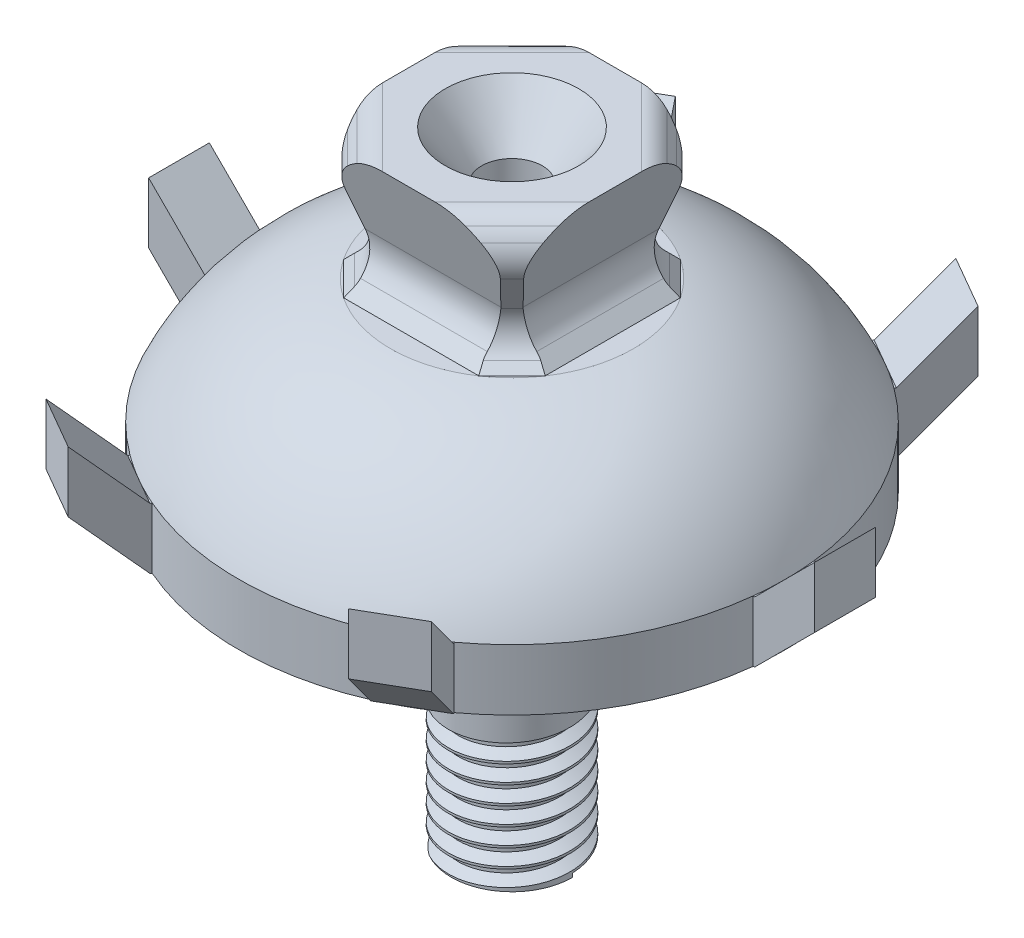
SolidWorks part; units mm, degrees
material "Commercially Pure CP-Ti UNS R50400 (SS)"
ref_plane "Front Plane" through (0, 0, 0) normal (0, 0, 1) x (1, 0, 0)
ref_plane "Top Plane" through (0, 0, 0) normal (0, 1, 0) x (1, 0, 0)
ref_plane "Right Plane" through (0, 0, 0) normal (1, 0, 0) x (0, 0, -1)
sketch "Sketch4" plane through (0, 0, 0) normal (0, 0, 1) x (1, 0, 0)
  line L1 (-8.5, -5.5) -> (8.5, -5.5)
  line L2 (-8.5, -5.5) -> (-8.5, 5.5)
  line L3 (-8.5, 5.5) -> (8.5, 5.5)
  line L4 (8.5, -5.5) -> (8.5, 5.5)
  line L5 (-8.5, -5.5) -> (8.5, 5.5) construction
  line L6 (-8.5, 5.5) -> (8.5, -5.5) construction
  point P0 (0, 0)
  dimension "D1" = 11
  dimension "D2" = 17
extrude "Boss-Extrude2" add sketch "Sketch4" along normal mid plane 17
sketch "Sketch5" plane through (0, 0, 0) normal (1, 0, 0) x (0, 0, -1)
  line L0 (0, -10) -> (0, 10) construction
  line L1 (8.5, 5.5) -> (6.5025, -1.2915)
  line L2 (8.5, -5.5) -> (7.2593, -4.2593)
  line L3 (-8.5, -5.5) -> (-7.2593, -4.2593)
  line L4 (-8.5, 5.5) -> (-6.5025, -1.2915)
  line L5 (-8.5, 5.5) -> (-8.5, -5.5)
  line L6 (8.5, -5.5) -> (8.5, 5.5)
  arc A0 (7.2593, -4.2593) -> (6.5025, -1.2915) centre (9.3806, -2.138) cw
  arc A1 (-7.2593, -4.2593) -> (-6.5025, -1.2915) centre (-9.3806, -2.138) ccw
  point P12 (6, -3)
  point P16 (-6, -3)
  dimension "D5" = 3
  dimension "D1" = 10
  dimension "D2" = 20
  dimension "D3" = 6
  dimension "D4" = 45
extrude "Cut-Extrude1" cut sketch "Sketch5" against normal mid plane 27
sketch "Sketch7" plane through (0, 0, 0) normal (0, 0, 1) x (1, 0, 0)
  line L0 (0, -10) -> (0, 10) construction
  line L1 (8.5, 5.5) -> (6.5025, -1.2915)
  line L2 (8.5, -5.5) -> (7.2593, -4.2593)
  line L3 (-8.5, -5.5) -> (-7.2593, -4.2593)
  line L4 (-8.5, 5.5) -> (-6.5025, -1.2915)
  line L5 (-8.5, 5.5) -> (-8.5, -5.5)
  line L6 (8.5, -5.5) -> (8.5, 5.5)
  line L7 (8.5, -4.2593) -> (8.5, -5.5) construction
  arc A0 (7.2593, -4.2593) -> (6.5025, -1.2915) centre (9.3806, -2.138) cw
  arc A1 (-7.2593, -4.2593) -> (-6.5025, -1.2915) centre (-9.3806, -2.138) ccw
  point P12 (-6, -3)
  dimension "D3" = 3
  dimension "D1" = 20
  dimension "D2" = 45
  dimension "D4" = 16.389
extrude "Cut-Extrude2" cut sketch "Sketch7" against normal mid plane 27
sketch "Sketch8" plane through (0, 5.5, 0) normal (0, 1, 0) x (1, 0, 0)
  line L0 (3.5355, 3.5355) -> (-3.5355, -3.5355) construction
  line L1 (-5, 0) -> (5, 0) construction
  line L2 (-3.5355, 3.5355) -> (3.5355, -3.5355) construction
  line L3 (0, 5) -> (0, -5) construction
  dimension "D1" = 10
  dimension "D2" = 10
  dimension "D3" = 10
  dimension "D4" = 45
  dimension "D5" = 45
  dimension "D6" = 10
sketch "Sketch9" plane through (0, 0, 0) normal (0, 1, 0) x (1, 0, 0)
  line L0 (3.5355, 3.5355) -> (-3.5355, -3.5355) construction
  line L1 (-5, 0) -> (5, 0) construction
  line L2 (-3.5355, 3.5355) -> (3.5355, -3.5355) construction
  line L3 (0, 5) -> (0, -5) construction
  point P8 (0, 0)
  point P10 (0, 0)
  point P11 (0, 0)
  dimension "D1" = 10
  dimension "D2" = 10
  dimension "D3" = 10
  dimension "D4" = 45
  dimension "D5" = 45
  dimension "D6" = 10
ref_plane "Plane1" through (0, 0, 0) normal (0.7071, 0, 0.7071) x (0.7071, 0, -0.7071)
ref_plane "Plane2" through (0, 0, 0) normal (0.7071, 0, -0.7071) x (-0.7071, 0, -0.7071)
sketch "Sketch11" plane through (0, 0, 0) normal (0.7071, 0, 0.7071) x (0.7071, 0, -0.7071)
  line L0 (-10, 5.5) -> (10, 5.5) construction
  line L1 (0, -5.5) -> (0, 5.5) construction
  line L2 (10, 5.5) -> (10, -5.5) construction
  line L3 (0, -5.5) -> (12.0208, -5.5) construction
  line L4 (10, -5.5) -> (0, -5.5) construction
  line L5 (10, -5.5) -> (9.1595, -4.6595)
  line L6 (10, 5.5) -> (10, 2.3) construction
  line L7 (0, 5.5) -> (8.25, 5.5) construction
  line L8 (9.6935, 1.5413) -> (8.4993, -1.4144)
  line L10 (10, -5.5) -> (14, -5.5)
  line L11 (14, -5.5) -> (14, 5.5)
  line L12 (14, 5.5) -> (8.25, 5.5)
  line L13 (-14, 5.5) -> (-8.25, 5.5)
  line L14 (-9.6935, 1.5413) -> (-8.4993, -1.4144)
  line L15 (-10, -5.5) -> (-9.1595, -4.6595)
  line L16 (-10, -5.5) -> (-14, -5.5)
  line L17 (-14, -5.5) -> (-14, 5.5)
  arc A0 (9.5819, 4.0331) -> (8.25, 5.5) centre (6.1993, 2.3) ccw
  arc A1 (9.5819, 4.0331) -> (9.6935, 1.5413) centre (6.9119, 2.6651) cw
  arc A2 (9.1595, -4.6595) -> (8.4993, -1.4144) centre (11.2808, -2.5382) cw
  arc A3 (-9.5819, 4.0331) -> (-9.6935, 1.5413) centre (-6.9119, 2.6651) ccw
  arc A4 (-9.5819, 4.0331) -> (-8.25, 5.5) centre (-6.1993, 2.3) cw
  arc A5 (-9.1595, -4.6595) -> (-8.4993, -1.4144) centre (-11.2808, -2.5382) ccw
  dimension "D7" = 3
  dimension "D8" = 3
  dimension "D1" = 20
  dimension "D2" = 11
  dimension "D3" = 45
  dimension "D4" = 8.25
  dimension "D5" = 3.2
  dimension "D6" = 22
  dimension "D9" = 4
extrude "Cut-Extrude3" cut sketch "Sketch11" against normal mid plane 27
sketch "Sketch12" plane through (0, 0, 0) normal (0.7071, 0, -0.7071) x (-0.7071, 0, -0.7071)
  line L0 (-10, 5.5) -> (10, 5.5) construction
  line L1 (0, -5.5) -> (0, 5.5) construction
  line L2 (10, 5.5) -> (10, -5.5) construction
  line L3 (10, -5.5) -> (0, -5.5) construction
  line L4 (10, -5.5) -> (9.1595, -4.6595)
  line L5 (10, 5.5) -> (10, 2.3) construction
  line L6 (0, 5.5) -> (8.25, 5.5) construction
  line L7 (9.6935, 1.5413) -> (8.4993, -1.4144)
  line L8 (10, -5.5) -> (14, -5.5)
  line L9 (14, -5.5) -> (14, 5.5)
  line L10 (14, 5.5) -> (8.25, 5.5)
  line L11 (-14, 5.5) -> (-8.25, 5.5)
  line L12 (-9.6935, 1.5413) -> (-8.4993, -1.4144)
  line L13 (-10, -5.5) -> (-9.1595, -4.6595)
  line L14 (-10, -5.5) -> (-14, -5.5)
  line L15 (-14, -5.5) -> (-14, 5.5)
  arc A0 (9.5819, 4.0331) -> (8.25, 5.5) centre (6.1993, 2.3) ccw
  arc A1 (9.5819, 4.0331) -> (9.6935, 1.5413) centre (6.9119, 2.6651) cw
  arc A2 (9.1595, -4.6595) -> (8.4993, -1.4144) centre (11.2808, -2.5382) cw
  arc A3 (-9.5819, 4.0331) -> (-9.6935, 1.5413) centre (-6.9119, 2.6651) ccw
  arc A4 (-9.5819, 4.0331) -> (-8.25, 5.5) centre (-6.1993, 2.3) cw
  arc A5 (-9.1595, -4.6595) -> (-8.4993, -1.4144) centre (-11.2808, -2.5382) ccw
  dimension "D7" = 3
  dimension "D8" = 3
  dimension "D1" = 20
  dimension "D2" = 11
  dimension "D3" = 45
  dimension "D4" = 8.25
  dimension "D5" = 3.2
  dimension "D6" = 22
  dimension "D9" = 4
extrude "Cut-Extrude4" cut sketch "Sketch12" against normal mid plane 27
sketch "Sketch14" plane through (0, 0, 0) normal (0, 0, 1) x (1, 0, 0)
  line L0 (0, 5.5) -> (0, -5.5) construction
  line L1 (0, 5.5) -> (5.5, 5.5)
  line L2 (3.1673, 5.5) -> (8.5, 5.5) construction
  line L3 (5.5, 5.5) -> (5.5, 1.5) construction
  line L4 (0, 1.5) -> (2.5, 1.5) construction
  line L5 (2.5, 1.5) -> (5.5, 5.5)
  line L6 (2.5, 1.5) -> (2.5, -5.5)
  line L7 (-5.6421, -5.5) -> (5.6421, -5.5) construction
  line L8 (0, -5.5) -> (0, 5.5)
  line L9 (2.5, -5.5) -> (0, -5.5)
  dimension "D1" = 11
  dimension "D2" = 5.5
  dimension "D3" = 4
  dimension "D4" = 2.5
revolve "Cut-Revolve1" cut sketch "Sketch14" angle 360 about L8
fillet "Fillet1" radius 2 4 edges at (5.8336, 5.5, -5.8336) (-5.8336, 5.5, -5.8336) (-5.8336, 5.5, 5.8336) (5.8336, 5.5, 5.8336)
sketch "Sketch15" plane through (0, 0, 0) normal (1, 0, 0) x (0, 0, -1)
  line L0 (0, -45.5) -> (0, -5.5)
  line L1 (-5.6421, -5.5) -> (5.6421, -5.5) construction
  line L5 (0, -5.5) -> (0, -5.3)
  line L6 (0, -5.3) -> (9.998, -5.3)
  line L13 (22.5, -15.5) -> (22.5, -20.5241)
  line L14 (5, -25.9041) -> (22.5, -20.5241)
  line L18 (0, -45.5) -> (5, -45.5)
  line L19 (5, -25.9041) -> (5, -45.5)
  arc A0 (9.998, -5.3) -> (22.5, -15.5) centre (6.077, -22.8677) cw
  dimension "D4" = 18
  dimension "D1" = 22.5
  dimension "D2" = 10
  dimension "D5" = 0.2
  dimension "D7" = 5
revolve "Revolve1" add sketch "Sketch15" angle 360 about L0
thread "Thread1" pitch 1.5 method cut profile "Thread Profile3" start angle 0, offset 1, length 11, pitch 1.5, diameter 10
ref_plane "Plane7" through (5, -46.5, 0) normal (0, 0, 1) x (1, 0, 0)
sketch "Thread Profile3" plane through (5, -46.5, 0) normal (0, 0, 1) x (1, 0, 0)
  line L0 (0, 0) -> (0, 1.5) construction
  line L11 (0, 0) -> (0, 1.3125)
  line L12 (0, 1.3125) -> (-0.8119, 0.8437)
  line L13 (-0.8119, 0.8437) -> (-0.8119, 0.4687)
  line L15 (-0.8119, 0.4687) -> (0, 0)
  line L17 (-0.8119, 0.6562) -> (0, 0.6562) construction
  point P2 (0, 0)
  dimension "Pitch" = 1.5
  dimension "Profile_Angle" = 60
  dimension "Profile_Land" = 0.375
  dimension "Profile_Height" = 0.8119
sketch "Sketch16" plane through (0, 0, 0) normal (0, 0, 1) x (1, 0, 0)
  line L0 (22.5, -15.5) -> (27.4257, -10.5743)
  line L1 (27.4257, -10.5743) -> (27.4257, -15.5743)
  line L2 (27.4257, -15.5743) -> (22.4759, -20.5241)
  line L3 (22.5, -20.5241) -> (-22.5, -20.5241) construction
  line L5 (22.5, -20.5241) -> (22.5, -15.5) construction
  line L6 (22.5, -15.5) -> (16.5, -15.5)
  line L7 (22.5, -15.5) -> (-22.5, -15.5) construction
  line L8 (16.5, -15.5) -> (16.5, -20.5241)
  line L9 (16.5, -20.5241) -> (22.4759, -20.5241)
  dimension "D1" = 5
  dimension "D2" = 45
  dimension "D3" = 7
  dimension "D4" = 45
  dimension "D5" = 6
extrude "Boss-Extrude3" add sketch "Sketch16" along normal mid plane 5
pattern_circular "CirPattern1" count 6 every 60 about axis through (0, -45.5, 0) along (0, -1, 0) of "Boss-Extrude3"
